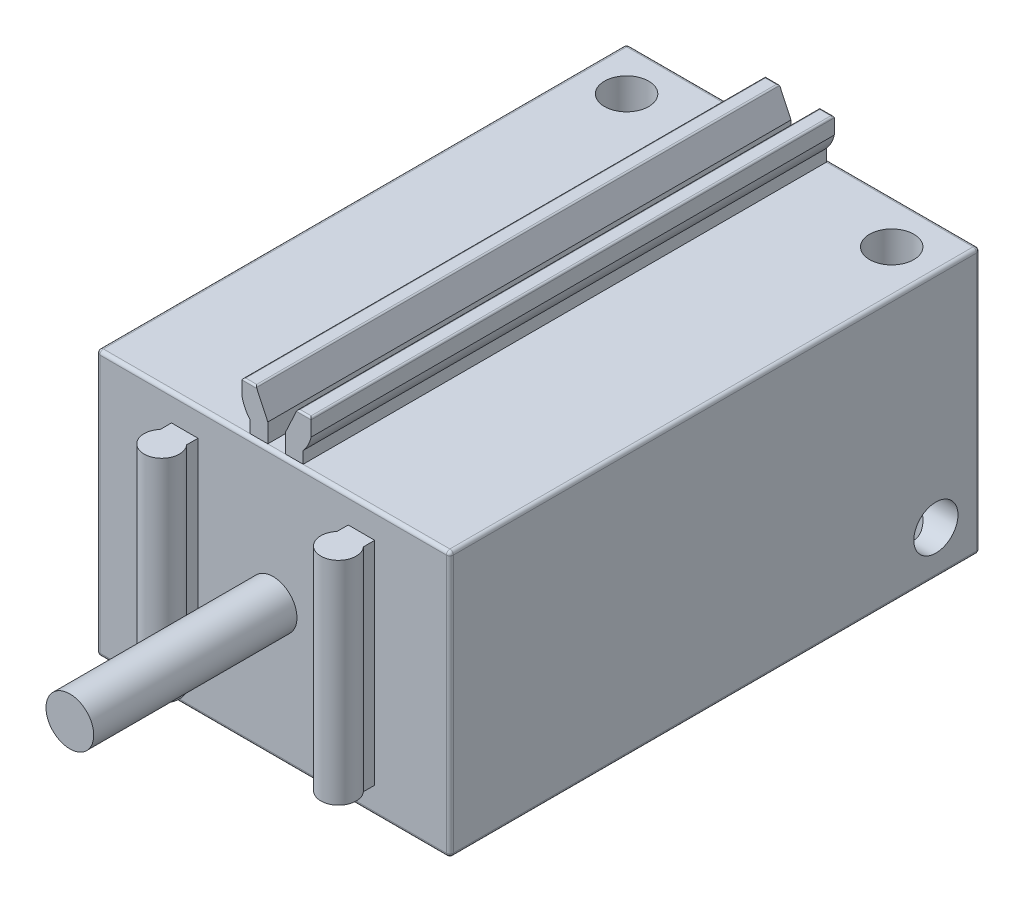
SolidWorks part; units mm, degrees
ref_plane "前视基准面" through (0, 0, 0) normal (0, 0, 1) x (1, 0, 0)
ref_plane "上视基准面" through (0, 0, 0) normal (0, 1, 0) x (1, 0, 0)
ref_plane "右视基准面" through (0, 0, 0) normal (1, 0, 0) x (0, 0, -1)
sketch "草图1" plane through (0, 0, 0) normal (0, 0, 1) x (1, 0, 0)
  line L1 (-10, -7.5) -> (10, -7.5)
  line L2 (-10, -7.5) -> (-10, 7.5)
  line L3 (-10, 7.5) -> (10, 7.5)
  line L4 (10, -7.5) -> (10, 7.5)
extrude "凸台-拉伸1" add sketch "草图1" against normal blind 30
sketch "草图2" plane through (0, 0, 0) normal (0, 1, 0) x (1, 0, 0)
  line L0 (-4.25, 0) -> (-5.75, 0)
  line L1 (-10, 0) -> (10, 0) construction
  line L2 (0, 1.4026) -> (0, -4.7973) construction
  line L3 (-5.75, 0) -> (-5.75, -0.6386)
  line L4 (-4.25, 0) -> (-4.25, -0.6386)
  line L5 (4.25, 0) -> (4.25, -0.6386)
  line L6 (5.75, 0) -> (5.75, -0.6386)
  line L7 (4.25, 0) -> (5.75, 0)
  arc A0 (-5.75, -0.6386) -> (-4.25, -0.6386) centre (-5, -1.3) ccw
  arc A1 (5.75, -0.6386) -> (4.25, -0.6386) centre (5, -1.3) cw
extrude "凸台-拉伸2" add sketch "草图2" along normal blind 6 and the other way blind 6
sketch "草图3" plane through (0, 0, 0) normal (0, 0, 1) x (1, 0, 0)
  circle A0 centre (0, 0) radius 1.35
extrude "凸台-拉伸3" add sketch "草图3" along normal blind 11.5
sketch "草图4" plane through (0, 0, 0) normal (0, 0, 1) x (1, 0, 0)
  line L0 (-1.5, 7.5) -> (-1.5, 8.1771)
  line L1 (10, 7.5) -> (-10, 7.5) construction
  line L2 (1.5, 7.5) -> (1.5, 8.1771)
  line L3 (-1.95, 10) -> (-1.1658, 10)
  line L4 (-1.95, 10) -> (-1.95, 9.0556)
  line L5 (1.95, 10) -> (1.95, 9.0556)
  line L6 (0, 7.1716) -> (0, 10.4474) construction
  line L7 (-1.5, 7.5) -> (-0.5, 7.5)
  line L8 (-0.5, 7.5) -> (-0.5, 8.5723)
  line L9 (0.5, 7.5) -> (0.5, 8.5723)
  line L10 (0.5, 8.5723) -> (1.1658, 10)
  line L11 (-0.5, 8.5723) -> (-1.1658, 10)
  line L12 (1.1658, 10) -> (1.95, 10)
  line L13 (0.5, 7.5) -> (1.5, 7.5)
  arc A1 (1.5, 8.1771) -> (1.95, 9.0556) centre (0, 9.5) ccw
  arc A2 (-1.95, 9.0556) -> (-1.5, 8.1771) centre (0, 9.5) ccw
extrude "凸台-拉伸4" add sketch "草图4" against normal blind 29.6 from offset 0.2 offset against normal yes
sketch "草图5" plane through (0, 7.5, 0) normal (0, 1, 0) x (-1, 0, 0)
  line L0 (1.5, -30) -> (1.5, -30.6771)
  line L1 (-10, -30) -> (10, -30) construction
  line L2 (-1.5, -30) -> (-1.5, -30.6771)
  line L3 (1.95, -32.5) -> (1.1658, -32.5)
  line L4 (1.95, -32.5) -> (1.95, -31.5556)
  line L5 (-1.95, -32.5) -> (-1.95, -31.5556)
  line L6 (1.5, -30) -> (0.5, -30)
  line L7 (0, -32.8437) -> (0, -29.6397) construction
  line L8 (-1.1658, -32.5) -> (1.1658, -32.5)
  line L9 (-0.5, -30) -> (0.5, -30)
  line L12 (-1.1658, -32.5) -> (-1.95, -32.5)
  line L13 (-0.5, -30) -> (-1.5, -30)
  arc A1 (-1.5, -30.6771) -> (-1.95, -31.5556) centre (0, -32) ccw
  arc A2 (1.95, -31.5556) -> (1.5, -30.6771) centre (0, -32) ccw
extrude "凸台-拉伸5" add sketch "草图5" against normal blind 14.6 from offset 0.2 offset against normal yes
fillet "圆角1" radius 0.1 12 edges at (1.1658, 10, -15) (1.5579, 10, -29.8) (1.95, 10, -15) (1.5579, 10, -0.2) (-1.95, 10, -15) (-1.5579, 10, -29.8) (-1.1658, 10, -15) (-1.5579, 10, -0.2) (0, -7.3, -32.5) (1.95, 0, -32.5) (0, 7.3, -32.5) (-1.95, 0, -32.5)
fillet "圆角2" radius 0.2 12 edges at (-10, -7.5, -15) (-10, 0, -30) (-10, 7.5, -15) (-10, 0, 0) (10, 7.5, -15) (10, 0, -30) (10, -7.5, -15) (10, 0, 0) (0, -7.5, -30) (0, 7.5, -30) (0, -7.5, 0) (0, 7.5, 0)
sketch "草图6" plane through (0, 7.5, 0) normal (0, 1, 0) x (-1, 0, 0)
  circle A0 centre (7.5, -27.5) radius 1.25
  circle A1 centre (-7.5, -27.5) radius 1.25
extrude "切除-拉伸1" cut sketch "草图6" against normal through all
sketch "草图7" plane through (-10, 0, 0) normal (-1, 0, 0) x (0, 0, 1)
  circle A0 centre (-27.5, -5) radius 1.25
extrude "切除-拉伸2" cut sketch "草图7" against normal through all
sketch "草图8" plane through (0, 0, -30) normal (0, 0, -1) x (-1, 0, 0)
  circle A0 centre (-7.5, 0) radius 1.25
  circle A1 centre (7.5, 0) radius 1.25
extrude "切除-拉伸3" cut sketch "草图8" against normal blind 5
sketch "草图9" plane through (0, 0, 0) normal (1, 0, 0) x (0, 0, -1)
  line L0 (30, 0) -> (32.5, 0) construction
  line L1 (30, -7.3) -> (30, 7.3) construction
  line L2 (32.5, 7.2) -> (32.5, -7.2) construction
  line L3 (30, 0) -> (32, 0) construction
  line L4 (32.5, 1.95) -> (31.5556, 1.95)
  line L5 (30, 0) -> (30, -1.5) construction
  line L6 (30, -1.5) -> (30.6771, -1.5)
  line L7 (32.5, 0) -> (32.5, -1.95) construction
  line L8 (32.5, -1.95) -> (31.5556, -1.95)
  line L9 (30, 1.5) -> (30.6771, 1.5)
  line L10 (32.5, 1.95) -> (32.5, 7.95)
  line L11 (32.5, 7.95) -> (30, 7.95)
  line L12 (30, 7.95) -> (30, 1.5)
  line L13 (32.5, -1.95) -> (32.5, -7.95)
  line L14 (32.5, -7.95) -> (30, -7.95)
  line L15 (30, -7.95) -> (30, -1.5)
  arc A0 (30.6771, -1.5) -> (31.5556, -1.95) centre (32, 0) ccw
  arc A1 (30.6771, 1.5) -> (31.5556, 1.95) centre (32, 0) cw
  dimension "D4" = 2
  dimension "D1" = 2
  dimension "D2" = 1.5
  dimension "D3" = 1.95
  dimension "D5" = 6
extrude "切除-拉伸4" cut sketch "草图9" against normal blind 5 and the other way blind 5
fillet "圆角3" radius 0.1 10 edges at (1.95, 1.95, -31.9778) (1.9207, 1.95, -32.4707) (-1.95, 1.95, -31.9778) (-1.9207, 1.95, -32.4707) (1.95, -1.95, -31.9778) (1.9207, -1.95, -32.4707) (-1.95, -1.95, -31.9778) (-1.9207, -1.95, -32.4707) (0, 1.95, -32.5) (0, -1.95, -32.5)
